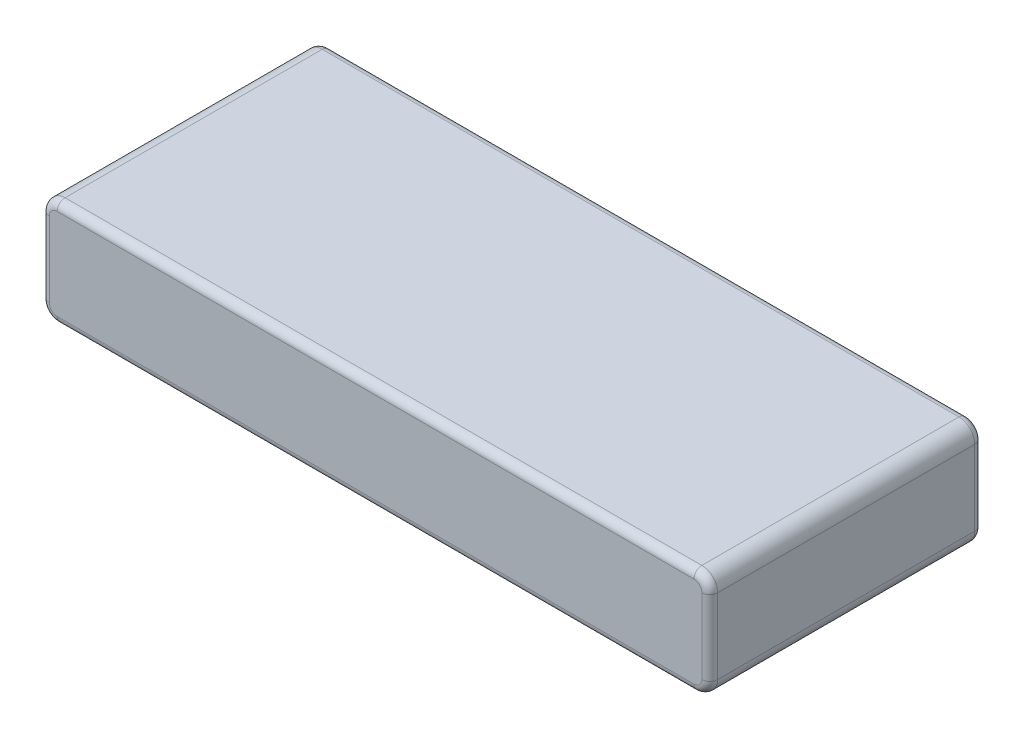
SolidWorks part; units mm, degrees
ref_plane "Płaszczyzna przednia" through (0, 0, 0) normal (0, 0, 1) x (1, 0, 0)
ref_plane "Płaszczyzna górna" through (0, 0, 0) normal (0, 1, 0) x (1, 0, 0)
ref_plane "Płaszczyzna prawa" through (0, 0, 0) normal (1, 0, 0) x (0, 0, -1)
sketch "Szkic1" plane through (0, 0, 0) normal (0, 1, 0) x (1, 0, 0)
  line L1 (84.5, -34.5) -> (-84.5, -34.5)
  line L2 (84.5, -34.5) -> (84.5, 34.5)
  line L3 (84.5, 34.5) -> (-84.5, 34.5)
  line L4 (-84.5, -34.5) -> (-84.5, 34.5)
  line L5 (84.5, -34.5) -> (-84.5, 34.5) construction
  line L6 (84.5, 34.5) -> (-84.5, -34.5) construction
  point P0 (0, 0)
  dimension "D1" = 169
  dimension "D2" = 69
extrude "Dodanie-wyciągnięcie1" add sketch "Szkic1" along normal blind 27
sketch "Szkic2" plane through (-84.5, 0, 0) normal (-1, 0, 0) x (0, 0, 1)
  line L2 (-14.0593, 12.379) -> (-32.5, 18.9762) construction
  line L3 (-34.5, 27) -> (-34.5, 0) construction
  line L4 (-34.5, 0) -> (34.5, 0) construction
  arc A0 (-13.6967, 11.7224) -> (-13.3625, 12.6566) centre (-13, 12) ccw
  arc A1 (-13.3625, 12.6566) -> (-13.6967, 11.7224) centre (-14.0593, 12.379) ccw
  dimension "D1" = 1.5
  dimension "D2" = 0.75
  dimension "D6" = 12
  dimension "D3" = 1.125
  dimension "D5" = 2
extrude "Dodanie-wyciągnięcie2" add sketch "Szkic2" along normal blind 10
fillet "Zaokrąglenie1" radius 4 4 edges at (84.5, 0, 0) (84.5, 27, 0) (-84.5, 0, 0) (-84.5, 27, 0)
fillet "Zaokrąglenie2" radius 2 16 edges at (83.3284, 25.8284, 34.5) (84.5, 13.5, 34.5) (83.3284, 1.1716, 34.5) (0, 0, 34.5) (-83.3284, 1.1716, 34.5) (-84.5, 13.5, 34.5) (-83.3284, 25.8284, 34.5) (83.3284, 25.8284, -34.5) (84.5, 13.5, -34.5) (83.3284, 1.1716, -34.5) (-83.3284, 1.1716, -34.5) (-83.3284, 25.8284, -34.5) (-84.5, 13.5, -34.5) (0, 27, 34.5) (0, 0, -34.5) (0, 27, -34.5)
